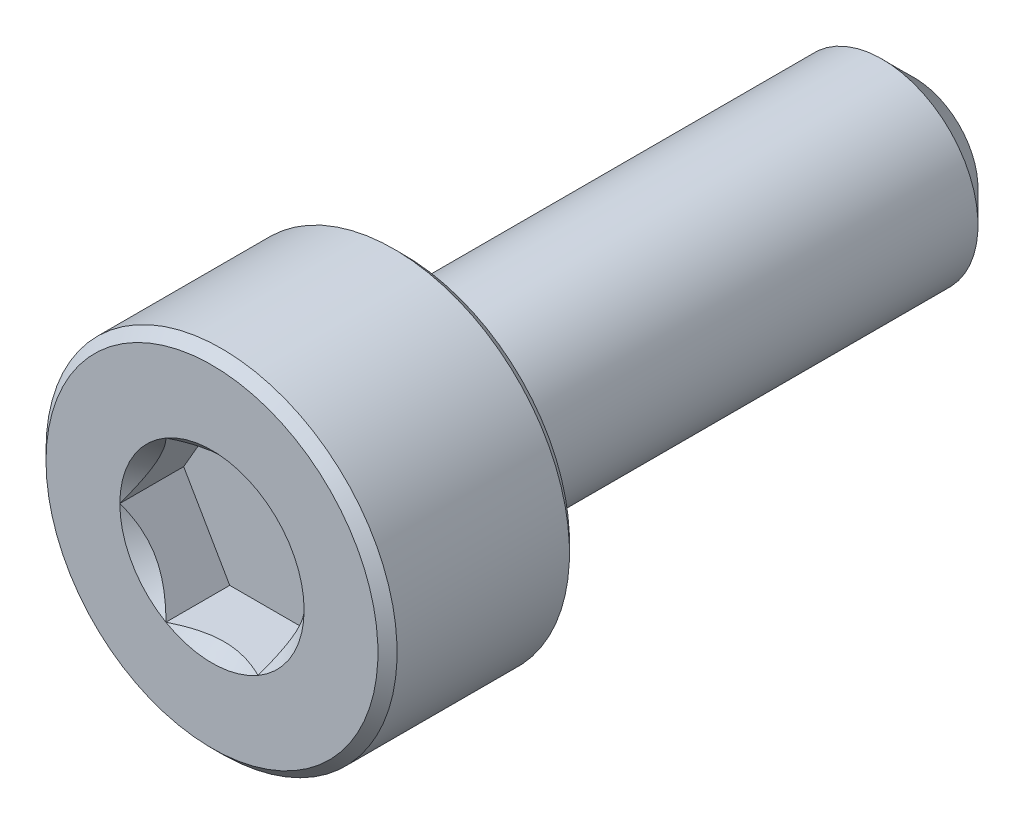
SolidWorks part; units mm, degrees
ref_plane "Front Plane" through (0, 0, 0) normal (0, 0, 1) x (1, 0, 0)
ref_plane "Top Plane" through (0, 0, 0) normal (0, 1, 0) x (1, 0, 0)
ref_plane "Right Plane" through (0, 0, 0) normal (1, 0, 0) x (0, 0, -1)
sketch "Sketch1" plane through (0, 0, 0) normal (1, 0, 0) x (0, 0, -1)
  line L0 (-5.5, 0) -> (5.5, 0) construction
  line L1 (5.5, 0) -> (5.5, 1) construction
  line L2 (5.5, 1) -> (5, 1.5) construction
  line L3 (5, 1.5) -> (-12.5, 1.5) construction
  line L5 (-2.5, 1.5) -> (-2.5, 2.75) construction
  line L6 (-2.5, 2.75) -> (-5.5, 2.75) construction
  line L7 (-5.5, 2.75) -> (-5.5, 0) construction
  line L8 (5.5, 1) -> (5.5, 1.5) construction
  line L9 (5.4688, 1.5541) -> (5.7188, 1.1211) construction
  line L10 (5.7188, 1.1211) -> (5.9688, 1.5541) construction
  line L11 (5.9688, 1.5541) -> (5.4688, 1.5541) construction
  line L12 (5.7188, 1.5541) -> (5.7188, 1.5) construction
  line L13 (5.7188, 1.1211) -> (5.7188, 1.1752) construction
  line L14 (5.6875, 1.1752) -> (5.75, 1.1752) construction
  line L15 (5.5, 1.5) -> (5.9375, 1.5) construction
  line L16 (5.4844, 1.5271) -> (5.9531, 1.5271) construction
  line L17 (5.5, 0) -> (5.5, -1.5) construction
  line L18 (-2.65, 2.75) -> (-2.5, 2.6) construction
  line L19 (-5.35, 2.75) -> (-5.5, 2.6) construction
  point P0 (-5.5, 1.25)
  point P3 (3.75, 1.5)
  point P4 (0, 0)
  point P22 (5.7188, 1.1752)
  point P24 (-12.5, 1.5)
  point P25 (5.7188, 1.5)
  point P28 (5.7188, 1.5271)
  point P29 (3.75, -1.5)
  point P31 (-4, 2.75)
  point P37 (-3.025, 2.75)
  point P38 (-5.275, 2.75)
  dimension "head height" = 3
  dimension "D1" = 45
  dimension "head dia" = 5.5
  dimension "thread dia" = 3
  dimension "drive size" = 2.5
  dimension "pitch" = 0.5
  dimension "D2" = 0.0625
  dimension "D3" = 0.5
  dimension "D4" = 1.75
  dimension "D7" = 0.15
  dimension "D8" = 0.15
  dimension "D9" = 0.15
  dimension "D10" = 0.075
  dimension "D11" = 0.375
  dimension "D12" = 18
  dimension "length" = 8
sketch "Sketch2" plane through (0, 0, 0) normal (1, 0, 0) x (0, 0, -1)
  line L1 (-5.35, 2.75) -> (-2.65, 2.75)
  line L4 (5, 1.5) -> (5.5, 1)
  line L5 (5.5, 1) -> (5.5, 0)
  line L6 (-2.65, 2.75) -> (-2.5, 2.6) construction
  line L7 (5.5, 0) -> (-5.5, 0)
  line L8 (-5.35, 2.75) -> (-5.5, 2.6) construction
  line L9 (-2.65, 2.75) -> (-2.5, 2.6)
  line L10 (-5.35, 2.75) -> (-5.5, 2.6)
  line L11 (-5.5, 2.6) -> (-5.5, 0)
  line L12 (-2.5, 2.6) -> (-2.5, 1.5)
  line L13 (-2.5, 1.5) -> (5, 1.5)
revolve "Revolve1" add sketch "Sketch2" angle 360 about L7
sketch "Sketch3" plane through (0, 0, 5.5) normal (0, 0, 1) x (1, 0, 0)
  line L1 (0.7217, 1.25) -> (-0.7217, 1.25)
  line L2 (-0.7217, 1.25) -> (-1.4434, 0)
  line L3 (-1.4434, 0) -> (-0.7217, -1.25)
  line L4 (-0.7217, -1.25) -> (0.7217, -1.25)
  line L5 (0.7217, -1.25) -> (1.4434, 0)
  line L6 (1.4434, 0) -> (0.7217, 1.25)
  circle A0 centre (0, 0) radius 1.25 construction
extrude "Cut-Extrude1" cut sketch "Sketch3" against normal offset from surface (1 mm away) 1 up to face at (-2.6, 0, 5.5)
sketch "Sketch4" plane through (0, 0, 5.5) normal (0, 0, 1) x (1, 0, 0)
  circle A0 centre (0, 0) radius 1.4434
extrude "Cut-Extrude2" cut sketch "Sketch4" against normal blind 0.5 draft 45
ref_plane "Plane1" [suppressed] through (0, 0, 12.5) normal (0, 0, 1) x (1, 0, 0)
split "Split1" [suppressed] bodies to split 106
sketch "Sketch6" [suppressed] plane through (0, 0, -5.5) normal (0, 0, -1) x (-1, 0, 0)
  circle A0 centre (0, 0) radius 1.5
curve "Helix/Spiral1" [suppressed] pitch 0.5 height 8.5 turns 17
sketch "Sketch7" [suppressed] plane through (0, 0, 0) normal (1, 0, 0) x (0, 0, -1)
  line L0 (5.4844, 1.5271) -> (5.9531, 1.5271)
  line L1 (5.9531, 1.5271) -> (5.75, 1.1752)
  line L2 (5.75, 1.1752) -> (5.6875, 1.1752)
  line L3 (5.6875, 1.1752) -> (5.4844, 1.5271)
sweep "Cut-Sweep1" [suppressed] cut profiles "Sketch7" path "Helix/Spiral1"
sketch "Sketch8" [suppressed] plane through (0, 0, 2.5) normal (0, 0, -1) x (-1, 0, 0)
  circle A0 centre (0, 0) radius 1.5
extrude "Boss-Extrude1" [suppressed] add sketch "Sketch8" along normal through all draft 45
ref_plane "Plane2" [suppressed] through (0, 0, 4) normal (0, 0, 1) x (1, 0, 0)
sketch "Sketch9" [suppressed] plane through (0, 0, 4) normal (0, 0, 1) x (1, 0, 0)
  line L0 (0, 2.6125) -> (0.048, 2.7496)
  line L1 (0, 2.6125) -> (-0.048, 2.7496)
  line L2 (0, 2.75) -> (0, 0) construction
  line L3 (-0.048, 2.7496) -> (0, 0) construction
  line L4 (0, 0) -> (0.048, 2.7496) construction
  arc A0 (0.048, 2.7496) -> (-0.048, 2.7496) centre (0, 0) ccw
  circle A1 centre (0, 0) radius 2.6125 construction
  dimension "D1" = 5.5
  dimension "D2" = 5.225
  dimension "D3" = 2
extrude "Cut-Extrude4" [suppressed] cut sketch "Sketch9" against normal up to vertex and the other way up to vertex up to point (0, 2.75, 3.025) other way up to point (0, 2.75, 5.275)
pattern_circular "CirPattern2" [suppressed] count 175 over 360 about axis through (0, 0, 5.5) along (0, 0, -1) of bodies 113
equation "\"D2@Sketch1\"=\"pitch@Sketch1\"/8"
equation "\"D3@Sketch1\"=\"pitch@Sketch1\""
equation "\"D3@Helix/Spiral1\"=\"length@Sketch1\"+\"pitch@Sketch1\""
equation "\"D4@Helix/Spiral1\"=\"pitch@Sketch1\""
equation "\"D4@Sketch1\"=\"pitch@Sketch1\"*3.5"
equation "\"D7@Sketch1\"=\"head height@Sketch1\"*.05"
equation "\"D8@Sketch1\"=\"D7@Sketch1\""
equation "\"D9@Sketch1\"=\"D7@Sketch1\""
equation "\"D10@Sketch1\"=\"D7@Sketch1\"/2"
equation "\"D11@Sketch1\"=\"D10@Sketch1\"*5"
equation "\"D2@Sketch9\"=\"D1@Sketch9\"*.95"
equation "\"D1@CirPattern2\"= ( 360 / \"D3@Sketch9\" ) - 5"
